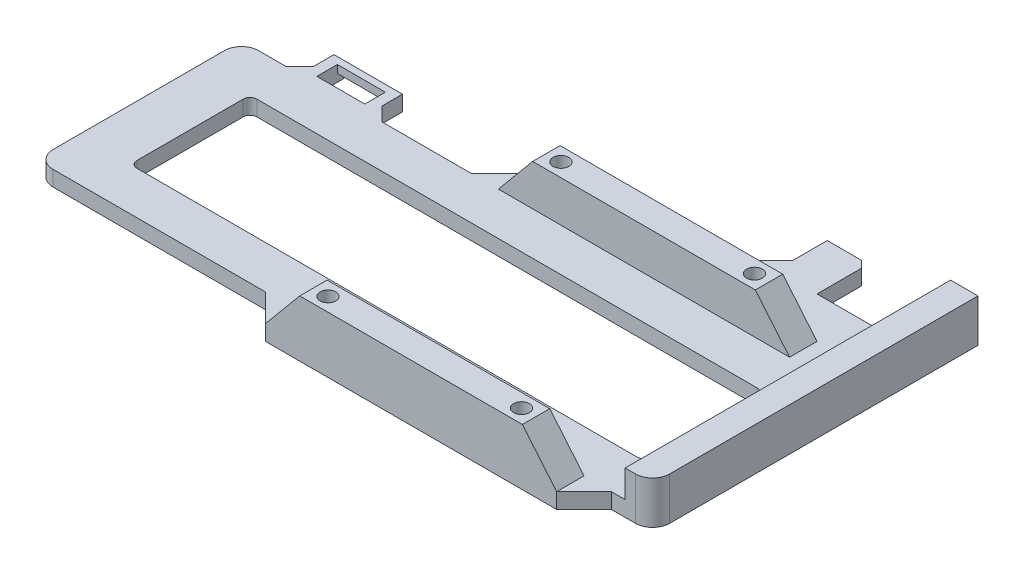
SolidWorks part; units mm, degrees
ref_plane "Front Plane" through (0, 0, 0) normal (0, 0, 1) x (1, 0, 0)
ref_plane "Top Plane" through (0, 0, 0) normal (0, 1, 0) x (1, 0, 0)
ref_plane "Right Plane" through (0, 0, 0) normal (1, 0, 0) x (0, 0, -1)
sketch "Sketch1" plane through (0, 0, 0) normal (0, 1, 0) x (1, 0, 0)
  line L0 (90, 60) -> (90, 0) construction
  line L1 (0, 0) -> (180, 0)
  line L2 (0, 0) -> (0, 60)
  line L3 (0, 60) -> (180, 60)
  line L4 (180, 0) -> (180, 60)
  line L5 (0, 30) -> (180, 30) construction
  line L7 (15, 12.5) -> (165, 12.5)
  line L8 (15, 12.5) -> (15, 47.5)
  line L9 (15, 47.5) -> (165, 47.5)
  line L10 (165, 12.5) -> (165, 47.5)
  line L11 (15, 12.5) -> (165, 47.5) construction
  line L12 (15, 47.5) -> (165, 12.5) construction
  point P9 (90, 30)
  dimension "D1" = 180
  dimension "D2" = 60
extrude "Boss-Extrude1" add sketch "Sketch1" along normal blind 4.5
fillet "Fillet1" radius 5 3 edges at (180, 2.25, 0) (0, 2.25, -60) (0, 2.25, 0)
fillet "Fillet2" radius 2 4 edges at (15, 2.25, -12.5) (165, 2.25, -12.5) (165, 2.25, -47.5) (15, 2.25, -47.5)
sketch "Sketch2" plane through (0, 4.5, 0) normal (0, 1, 0) x (1, 0, 0)
  line L5 (180, 80) -> (180, 60)
  line L6 (136, 60) -> (180, 60)
  line L7 (158, 60) -> (158, 88.8379) construction
  line L8 (136, 80) -> (136, 60)
  line L11 (148, 80) -> (168, 80)
  line L12 (180, 80) -> (180, 95)
  line L13 (180, 95) -> (168, 95)
  line L14 (168, 95) -> (168, 80)
  line L15 (136, 80) -> (136, 95)
  line L16 (136, 95) -> (148, 95)
  line L17 (148, 95) -> (148, 80)
  dimension "D1" = 20
  dimension "D2" = 15
extrude "Boss-Extrude2" add sketch "Sketch2" against normal up to surface (4.5 mm away) up to face at (77.7092, 0, -26.2806)
chamfer "Chamfer1" distance 25 angle 45 1 edges at (136, 2.25, -60)
chamfer "Chamfer2" distance 2 angle 45 2 edges at (168, 2.25, -95) (148, 2.25, -95)
sketch "Sketch3" plane through (0, 4.5, 0) normal (0, 1, 0) x (1, 0, 0)
  line L1 (5, 0) -> (175, 0) construction
  line L2 (90, -8) -> (160, -8)
  line L3 (160, -8) -> (160, 0)
  line L4 (160, 0) -> (90, 0)
  line L5 (15, 30) -> (165, 30) construction
  line L8 (160, 60) -> (90, 60)
  line L9 (160, 68) -> (160, 60)
  line L10 (90, 68) -> (160, 68)
  line L12 (90, -8) -> (75, -8)
  line L13 (75, -8) -> (75, 0)
  line L14 (75, 0) -> (90, 0)
  line L15 (90, 60) -> (75, 60)
  line L16 (111, 60) -> (5, 60) construction
  line L17 (75, 60) -> (75, 68)
  line L18 (75, 68) -> (90, 68)
  dimension "D1" = 8
  dimension "D2" = 70
extrude "Boss-Extrude3" add sketch "Sketch3" along normal blind 12 and the other way up to surface (4.5 mm away) contours L8 L15 L17 L18 L10 L9 | L4 L14 L13 L12 L2 L3 other way up to face at (117.1853, 0, -62.1853)
chamfer "Chamfer3" distance 10 distance2 12 3 edges at (160, 16.5, -64) (75, 16.5, -64) (75, 16.5, 4) first distance on face at (117.5, 16.5, -64) first distance on face at (117.5, 16.5, 4)
chamfer "Chamfer4" distance 8 angle 45 3 edges at (160, 2.25, 0) (75, 2.25, 0) (75, 2.25, -60)
sketch "Sketch4" plane through (0, 4.5, 0) normal (0, 1, 0) x (1, 0, 0)
  line L0 (180, 95) -> (180, 5)
  line L1 (180, 95) -> (172, 95)
  line L2 (180, 95) -> (170, 95) construction
  line L3 (172, 95) -> (172, 0)
  line L4 (168, 0) -> (175, 0) construction
  line L5 (172, 0) -> (175, 0)
  arc A0 (175, 0) -> (180, 5) centre (175, 5) ccw
extrude "Boss-Extrude4" add sketch "Sketch4" along normal blind 8
sketch "Sketch5" plane through (0, 16.5, 0) normal (0, 1, 0) x (1, 0, 0)
  line L0 (117.5, 68) -> (117.5, 60) construction
  line L1 (85, 68) -> (150, 68) construction
  line L2 (150, 60) -> (85, 60) construction
  line L3 (117.5, 64) -> (89.25, 64) construction
  line L4 (165, 30) -> (15, 30) construction
  line L5 (165, 14.5) -> (165, 45.5) construction
  line L6 (15, 45.5) -> (15, 14.5) construction
  circle A0 centre (89.25, 64) radius 2.3
  circle A1 centre (145.75, 64) radius 2.3
  circle A2 centre (145.75, -4) radius 2.3
  circle A3 centre (89.25, -4) radius 2.3
extrude "Cut-Extrude1" cut sketch "Sketch5" against normal blind 14
chamfer "Chamfer5" distance 12 distance2 10 1 edges at (160, 16.5, 4) first distance on face at (160, 10.5, 4)
sketch "Sketch6" plane through (0, 4.5, 0) normal (0, 1, 0) x (1, 0, 0)
  line L0 (5, 60) -> (17, 60)
  line L1 (67, 60) -> (5, 60) construction
  line L2 (17, 60) -> (17, 70)
  line L3 (17, 70) -> (37, 70)
  line L4 (37, 70) -> (37, 60)
  line L5 (37, 60) -> (17, 60)
  line L6 (27, 70) -> (27, 60) construction
  line L7 (17, 65) -> (37, 65) construction
  line L9 (20, 62) -> (34, 62)
  line L10 (20, 62) -> (20, 68)
  line L11 (20, 68) -> (34, 68)
  line L12 (34, 62) -> (34, 68)
  line L13 (20, 62) -> (34, 68) construction
  line L14 (20, 68) -> (34, 62) construction
  point P12 (27, 65)
  line M12 (165, 45.5) -> (165, 14.5)
  arc M13 (165, 14.5) -> (163, 12.5) centre (163, 14.5) cw
  line M14 (163, 12.5) -> (17, 12.5)
  arc M15 (17, 12.5) -> (15, 14.5) centre (17, 14.5) cw
  line M16 (15, 14.5) -> (15, 45.5)
  arc M17 (15, 45.5) -> (17, 47.5) centre (17, 45.5) cw
  line M18 (17, 47.5) -> (163, 47.5)
  arc M19 (163, 47.5) -> (165, 45.5) centre (163, 45.5) cw
  line M20 (172, 0) -> (172, 95)
  line M21 (172, 95) -> (170, 95)
  line M22 (170, 95) -> (168, 93)
  line M23 (168, 93) -> (168, 80)
  line M24 (168, 80) -> (148, 80)
  line M25 (148, 80) -> (148, 93)
  line M26 (148, 93) -> (146, 95)
  line M27 (146, 95) -> (136, 95)
  line M28 (136, 95) -> (136, 85)
  line M29 (136, 85) -> (119, 68)
  line M30 (119, 68) -> (160, 68)
  line M31 (160, 68) -> (160, 60)
  line M32 (160, 60) -> (75, 60)
  line M33 (75, 60) -> (75, 68)
  line M34 (75, 68) -> (67, 60)
  line M35 (67, 60) -> (5, 60)
  arc M36 (5, 60) -> (0, 55) centre (5, 55) ccw
  line M37 (0, 55) -> (0, 5)
  arc M38 (0, 5) -> (5, 0) centre (5, 5) ccw
  line M39 (5, 0) -> (67, 0)
  line M40 (67, 0) -> (75, -8)
  line M41 (75, -8) -> (75, 0)
  line M42 (75, 0) -> (160, 0)
  line M43 (160, 0) -> (160, -8)
  line M44 (160, -8) -> (168, 0)
  line M45 (168, 0) -> (172, 0)
  dimension "D1" = 12
  dimension "D2" = 10
extrude "Boss-Extrude5" add sketch "Sketch6" against normal up to surface (4.5 mm away) contours L4 L3 L2 L12 L9 L10 L11 M35 | M45 M20 M21 M22 M23 M24 M25 M26 M27 M28 M29 M30 M31 M32 M33 M34 M35 M36 M37 M38 M39 M40 M41 M42 M43 M44 M19 M12 M13 M14 M15 M16 M17 M18 region at (11, 4.5, -57.9952) region at (17.2236, 4.5, -65) up to face at (113.4075, 0, -50.6802)
chamfer "Chamfer6" distance 4 angle 45 2 edges at (37, 2.25, -60) (17, 2.25, -60)
sketch "Sketch7" plane through (0, 0, -68) normal (0, 0, 1) x (1, 0, 0)
  line L0 (34, 0) -> (34, 2.25)
  line L1 (34, 0) -> (34, 4.5) construction
  line L2 (34, 2.25) -> (20, 2.25)
  line L3 (20, 0) -> (20, 4.5) construction
  line L4 (20, 2.25) -> (20, 0)
  line L5 (20, 0) -> (34, 0)
extrude "Cut-Extrude2" cut sketch "Sketch7" against normal blind 3
